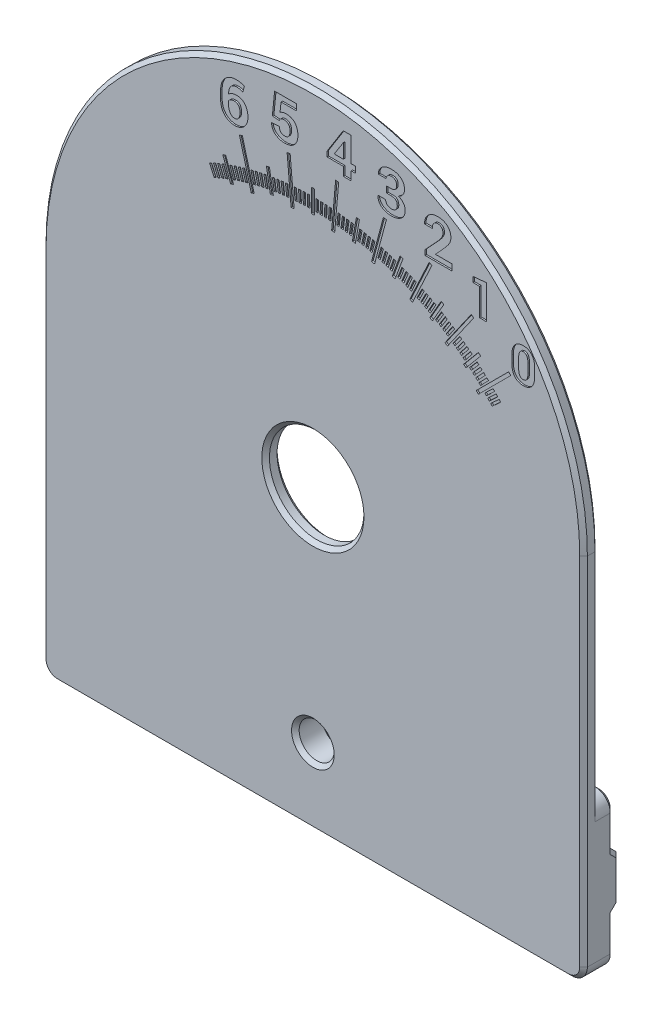
SolidWorks part; units mm, degrees
ref_plane "Front" through (0, 0, 0) normal (0, 0, 1) x (1, 0, 0)
ref_plane "Top" through (0, 0, 0) normal (0, 1, 0) x (1, 0, 0)
ref_plane "Right" through (0, 0, 0) normal (1, 0, 0) x (0, 0, -1)
sketch "Skizze1" plane through (0, 0, 0) normal (0, 0, 1) x (1, 0, 0)
  line L0 (0, 0) -> (35.5, 0)
  line L1 (0, 0) -> (0, 30.7358) construction
  line L2 (35.5, 5.5) -> (35.5, 0) construction
  line L3 (35.5, 0) -> (35.5, 28.6879)
  line L4 (-35.5, 0) -> (-35.5, 28.6879)
  line L5 (35.5, 0) -> (35.5, -20)
  line L6 (35.5, -20) -> (-35.5, -20)
  line L7 (-35.5, -20) -> (-35.5, 0)
  line L8 (-35.5, 0) -> (0, 0)
  arc A1 (35.5, 28.6879) -> (0, 64.1879) centre (0, 28.6879) ccw
  arc A2 (-35.5, 28.6879) -> (0, 64.1879) centre (0, 28.6879) cw
  dimension "D1" = 20
extrude "Aufsatz-Linear austragen1" add sketch "Skizze1" along normal blind 2 contours A2 L4 L8 L0 L3 A1 region at (0, 28.8397, 0)
sketch "Skizze2" plane through (0, 0, 2) normal (0, 0, 1) x (1, 0, 0)
  line L0 (0, 19) -> (0, 51.4601) construction
  line L1 (0, 19) -> (13.7352, 32.7352) construction
  line L2 (0, 19) -> (3.1812, 55.3611) construction
  line L3 (2.8575, 49.3665) -> (3.3804, 55.3437)
  line L4 (2.8575, 49.3665) -> (2.459, 49.4014)
  line L5 (3.3804, 55.3437) -> (3.1812, 55.3611)
  line L6 (2.9819, 55.3785) -> (3.1812, 55.3611)
  line L7 (2.459, 49.4014) -> (2.9819, 55.3785)
  line L8 (0, 19) -> (-2.3131, -14.0789) construction
  line L9 (2.3019, 51.9193) -> (2.4516, 51.9088)
  line L10 (2.4516, 51.9088) -> (2.3469, 50.4124)
  line L11 (2.3469, 50.4124) -> (2.0477, 50.4334)
  line L12 (2.1523, 51.9297) -> (2.0477, 50.4334)
  line L13 (2.3019, 51.9193) -> (2.1523, 51.9297)
  line L14 (0, 19) -> (-1.6664, -8.2459) construction
  line L15 (0, 19) -> (-1.7354, -14.1142) construction
  line L16 (1.5773, 51.9623) -> (1.4988, 50.4643)
  line L17 (1.7271, 51.9544) -> (1.5773, 51.9623)
  line L18 (1.7271, 51.9544) -> (1.8769, 51.9466)
  line L19 (1.8769, 51.9466) -> (1.7984, 50.4486)
  line L20 (1.4988, 50.4643) -> (1.7984, 50.4486)
  line L21 (0, 19) -> (-1.1573, -14.1395) construction
  line L22 (1.0018, 51.9848) -> (0.9494, 50.4857)
  line L23 (1.1517, 51.9795) -> (1.0018, 51.9848)
  line L24 (1.1517, 51.9795) -> (1.3016, 51.9743)
  line L25 (1.3016, 51.9743) -> (1.2492, 50.4752)
  line L26 (0.9494, 50.4857) -> (1.2492, 50.4752)
  line L27 (0, 19) -> (0, -14.1597) construction
  line L28 (0, 19) -> (-0.5787, -14.1546) construction
  line L34 (0.5759, 51.9946) -> (0.7259, 51.992)
  line L35 (0.5759, 51.9946) -> (0.4259, 51.9972)
  line L36 (0.4259, 51.9972) -> (0.3998, 50.4975)
  line L37 (0.6997, 50.4922) -> (0.3998, 50.4975)
  line L38 (0.7259, 51.992) -> (0.6997, 50.4922)
  line L39 (0, 53) -> (0.2, 53)
  line L40 (0.2, 53) -> (0.2, 50)
  line L41 (0.2, 50) -> (-0.2, 50)
  line L42 (-0.2, 53) -> (-0.2, 50)
  line L43 (0, 53) -> (-0.2, 53)
  line L44 (-2.4516, 51.9088) -> (-2.3469, 50.4124)
  line L45 (-2.3019, 51.9193) -> (-2.4516, 51.9088)
  line L46 (-2.3019, 51.9193) -> (-2.1523, 51.9297)
  line L47 (-2.1523, 51.9297) -> (-2.0477, 50.4334)
  line L48 (-2.3469, 50.4124) -> (-2.0477, 50.4334)
  line L49 (-1.7271, 51.9544) -> (-1.5773, 51.9623)
  line L50 (-1.7271, 51.9544) -> (-1.8769, 51.9466)
  line L51 (-1.8769, 51.9466) -> (-1.7984, 50.4486)
  line L52 (-1.4988, 50.4643) -> (-1.7984, 50.4486)
  line L53 (-1.5773, 51.9623) -> (-1.4988, 50.4643)
  line L54 (-1.1517, 51.9795) -> (-1.0018, 51.9848)
  line L55 (-1.1517, 51.9795) -> (-1.3016, 51.9743)
  line L56 (-1.3016, 51.9743) -> (-1.2492, 50.4752)
  line L57 (-0.9494, 50.4857) -> (-1.2492, 50.4752)
  line L58 (-1.0018, 51.9848) -> (-0.9494, 50.4857)
  line L59 (-0.5759, 51.9946) -> (-0.4259, 51.9972)
  line L60 (-0.4259, 51.9972) -> (-0.3998, 50.4975)
  line L61 (-0.6997, 50.4922) -> (-0.3998, 50.4975)
  line L62 (-0.7259, 51.992) -> (-0.6997, 50.4922)
  line L63 (-0.5759, 51.9946) -> (-0.7259, 51.992)
  line L64 (-2.459, 49.4014) -> (-2.9819, 55.3785)
  line L65 (-2.8575, 49.3665) -> (-2.459, 49.4014)
  line L66 (-2.8575, 49.3665) -> (-3.3804, 55.3437)
  line L67 (-3.3804, 55.3437) -> (-3.1812, 55.3611)
  line L68 (-2.9819, 55.3785) -> (-3.1812, 55.3611)
  line L69 (0, 19) -> (-3.1812, 55.3611) construction
  line L70 (-5.1623, 51.5934) -> (-5.0141, 51.6168)
  line L71 (-5.0141, 51.6168) -> (-4.7795, 50.1353)
  line L72 (-4.7795, 50.1353) -> (-5.0758, 50.0884)
  line L73 (-5.3104, 51.5699) -> (-5.0758, 50.0884)
  line L74 (-5.1623, 51.5934) -> (-5.3104, 51.5699)
  line L75 (-4.5927, 51.6785) -> (-4.4441, 51.6994)
  line L76 (-4.4441, 51.6994) -> (-4.2354, 50.214)
  line L77 (-4.5324, 50.1722) -> (-4.2354, 50.214)
  line L78 (-4.7412, 51.6576) -> (-4.5324, 50.1722)
  line L79 (-4.5927, 51.6785) -> (-4.7412, 51.6576)
  line L80 (-4.0216, 51.7537) -> (-3.8728, 51.7719)
  line L81 (-3.8728, 51.7719) -> (-3.69, 50.2831)
  line L82 (-3.9877, 50.2466) -> (-3.69, 50.2831)
  line L83 (-4.1705, 51.7354) -> (-3.9877, 50.2466)
  line L84 (-4.0216, 51.7537) -> (-4.1705, 51.7354)
  line L85 (-3.4494, 51.8189) -> (-3.3002, 51.8345)
  line L86 (-3.4494, 51.8189) -> (-3.5986, 51.8032)
  line L87 (-3.5986, 51.8032) -> (-3.4418, 50.3114)
  line L88 (-3.1434, 50.3428) -> (-3.4418, 50.3114)
  line L89 (-3.3002, 51.8345) -> (-3.1434, 50.3428)
  line L90 (-6.101, 52.4487) -> (-5.5801, 49.4943)
  line L91 (-5.904, 52.4835) -> (-6.101, 52.4487)
  line L92 (-5.904, 52.4835) -> (-5.7071, 52.5182)
  line L93 (-5.7071, 52.5182) -> (-5.1861, 49.5638)
  line L94 (-5.5801, 49.4943) -> (-5.1861, 49.5638)
  line L95 (0, 19) -> (-5.6366, 50.967) construction
  line L96 (0, 19) -> (-9.4469, 54.2563) construction
  line L97 (-7.7008, 48.5125) -> (-8.0872, 48.409)
  line L98 (-7.7008, 48.5125) -> (-9.2537, 54.3081)
  line L99 (-9.2537, 54.3081) -> (-9.4469, 54.2563)
  line L100 (-9.6401, 54.2045) -> (-9.4469, 54.2563)
  line L101 (-8.0872, 48.409) -> (-9.6401, 54.2045)
  line L102 (-7.9833, 51.0194) -> (-7.8378, 51.0557)
  line L103 (-7.8378, 51.0557) -> (-7.4749, 49.6003)
  line L104 (-7.766, 49.5277) -> (-7.4749, 49.6003)
  line L105 (-8.1289, 50.9831) -> (-7.766, 49.5277)
  line L106 (-7.9833, 51.0194) -> (-8.1289, 50.9831)
  line L107 (-7.4233, 51.1539) -> (-7.2771, 51.1876)
  line L108 (-7.2771, 51.1876) -> (-6.9397, 49.7261)
  line L109 (-6.9397, 49.7261) -> (-7.232, 49.6586)
  line L110 (-7.5695, 51.1201) -> (-7.232, 49.6586)
  line L111 (-7.4233, 51.1539) -> (-7.5695, 51.1201)
  line L112 (-6.861, 51.2785) -> (-6.7143, 51.3097)
  line L113 (-6.7143, 51.3097) -> (-6.4024, 49.8425)
  line L114 (-6.4024, 49.8425) -> (-6.6959, 49.7801)
  line L115 (-7.0077, 51.2473) -> (-6.6959, 49.7801)
  line L116 (-6.861, 51.2785) -> (-7.0077, 51.2473)
  line L117 (-6.2966, 51.3933) -> (-6.1494, 51.422)
  line L118 (-6.1494, 51.422) -> (-5.8632, 49.9495)
  line L119 (-6.1577, 49.8923) -> (-5.8632, 49.9495)
  line L120 (-6.4439, 51.3647) -> (-6.1577, 49.8923)
  line L121 (-6.2966, 51.3933) -> (-6.4439, 51.3647)
  line L122 (0, 19) -> (-11.102, 49.5026) construction
  line L123 (-11.6287, 50.9495) -> (-11.4407, 51.018)
  line L124 (-11.6287, 50.9495) -> (-11.8166, 50.8811)
  line L125 (-11.8166, 50.8811) -> (-10.7906, 48.0621)
  line L126 (-10.4147, 48.1989) -> (-10.7906, 48.0621)
  line L127 (-11.4407, 51.018) -> (-10.4147, 48.1989)
  line L128 (-10.7436, 50.2018) -> (-10.6018, 50.2506)
  line L129 (-10.6018, 50.2506) -> (-10.1135, 48.8323)
  line L130 (-10.1135, 48.8323) -> (-10.3971, 48.7347)
  line L131 (-10.8855, 50.1529) -> (-10.3971, 48.7347)
  line L132 (-10.7436, 50.2018) -> (-10.8855, 50.1529)
  line L133 (-10.1975, 50.3845) -> (-10.0548, 50.4309)
  line L134 (-10.0548, 50.4309) -> (-9.5913, 49.0043)
  line L135 (-9.8766, 48.9116) -> (-9.5913, 49.0043)
  line L136 (-10.3401, 50.3382) -> (-9.8766, 48.9116)
  line L137 (-10.1975, 50.3845) -> (-10.3401, 50.3382)
  line L138 (-9.6482, 50.5577) -> (-9.5047, 50.6016)
  line L139 (-9.5047, 50.6016) -> (-9.0662, 49.1671)
  line L140 (-9.353, 49.0794) -> (-9.0662, 49.1671)
  line L141 (-9.7916, 50.5139) -> (-9.353, 49.0794)
  line L142 (-9.6482, 50.5577) -> (-9.7916, 50.5139)
  line L143 (-9.0959, 50.7213) -> (-8.9517, 50.7626)
  line L144 (-8.9517, 50.7626) -> (-8.5383, 49.3207)
  line L145 (-8.5383, 49.3207) -> (-8.8267, 49.2381)
  line L146 (-9.2401, 50.6799) -> (-8.8267, 49.2381)
  line L147 (-9.0959, 50.7213) -> (-9.2401, 50.6799)
  line L148 (-13.4222, 49.1467) -> (-13.2851, 49.2077)
  line L149 (-13.2851, 49.2077) -> (-12.675, 47.8374)
  line L150 (-12.9491, 47.7153) -> (-12.675, 47.8374)
  line L151 (-13.5592, 49.0857) -> (-12.9491, 47.7153)
  line L152 (-13.4222, 49.1467) -> (-13.5592, 49.0857)
  line L153 (-12.894, 49.3763) -> (-12.7559, 49.4349)
  line L154 (-12.7559, 49.4349) -> (-12.1698, 48.0542)
  line L155 (-12.1698, 48.0542) -> (-12.446, 47.937)
  line L156 (-13.0321, 49.3177) -> (-12.446, 47.937)
  line L157 (-12.894, 49.3763) -> (-13.0321, 49.3177)
  line L158 (-12.3619, 49.5967) -> (-12.2228, 49.6529)
  line L159 (-12.2228, 49.6529) -> (-11.6609, 48.2622)
  line L160 (-11.6609, 48.2622) -> (-11.9391, 48.1498)
  line L161 (-12.501, 49.5405) -> (-11.9391, 48.1498)
  line L162 (-12.3619, 49.5967) -> (-12.501, 49.5405)
  line L163 (-11.826, 49.8078) -> (-11.686, 49.8616)
  line L164 (-11.686, 49.8616) -> (-11.1484, 48.4612)
  line L165 (-11.4285, 48.3537) -> (-11.1484, 48.4612)
  line L166 (-11.9661, 49.7541) -> (-11.4285, 48.3537)
  line L167 (-11.826, 49.8078) -> (-11.9661, 49.7541)
  line L168 (3.3002, 51.8345) -> (3.1434, 50.3428)
  line L169 (3.4494, 51.8189) -> (3.3002, 51.8345)
  line L170 (3.4494, 51.8189) -> (3.5986, 51.8032)
  line L171 (3.5986, 51.8032) -> (3.4418, 50.3114)
  line L172 (3.1434, 50.3428) -> (3.4418, 50.3114)
  line L173 (4.0216, 51.7537) -> (4.1705, 51.7354)
  line L174 (4.0216, 51.7537) -> (3.8728, 51.7719)
  line L175 (3.8728, 51.7719) -> (3.69, 50.2831)
  line L176 (3.9877, 50.2466) -> (3.69, 50.2831)
  line L177 (4.1705, 51.7354) -> (3.9877, 50.2466)
  line L178 (4.5927, 51.6785) -> (4.7412, 51.6576)
  line L179 (4.5927, 51.6785) -> (4.4441, 51.6994)
  line L180 (4.4441, 51.6994) -> (4.2354, 50.214)
  line L181 (4.5324, 50.1722) -> (4.2354, 50.214)
  line L182 (4.7412, 51.6576) -> (4.5324, 50.1722)
  line L183 (5.1623, 51.5934) -> (5.3104, 51.5699)
  line L184 (5.3104, 51.5699) -> (5.0758, 50.0884)
  line L185 (4.7795, 50.1353) -> (5.0758, 50.0884)
  line L186 (5.0141, 51.6168) -> (4.7795, 50.1353)
  line L187 (5.1623, 51.5934) -> (5.0141, 51.6168)
  line L188 (0, 19) -> (5.6366, 50.967) construction
  line L189 (5.7071, 52.5182) -> (5.1861, 49.5638)
  line L190 (5.904, 52.4835) -> (5.7071, 52.5182)
  line L191 (5.904, 52.4835) -> (6.101, 52.4487)
  line L192 (6.101, 52.4487) -> (5.5801, 49.4943)
  line L193 (5.1861, 49.5638) -> (5.5801, 49.4943)
  line L194 (6.2966, 51.3933) -> (6.4439, 51.3647)
  line L195 (6.4439, 51.3647) -> (6.1577, 49.8923)
  line L196 (6.1577, 49.8923) -> (5.8632, 49.9495)
  line L197 (6.1494, 51.422) -> (5.8632, 49.9495)
  line L198 (6.2966, 51.3933) -> (6.1494, 51.422)
  line L199 (6.861, 51.2785) -> (7.0077, 51.2473)
  line L200 (7.0077, 51.2473) -> (6.6959, 49.7801)
  line L201 (6.4024, 49.8425) -> (6.6959, 49.7801)
  line L202 (6.7143, 51.3097) -> (6.4024, 49.8425)
  line L203 (6.861, 51.2785) -> (6.7143, 51.3097)
  line L204 (7.4233, 51.1539) -> (7.5695, 51.1201)
  line L205 (7.5695, 51.1201) -> (7.232, 49.6586)
  line L206 (6.9397, 49.7261) -> (7.232, 49.6586)
  line L207 (7.2771, 51.1876) -> (6.9397, 49.7261)
  line L208 (7.4233, 51.1539) -> (7.2771, 51.1876)
  line L209 (7.9833, 51.0194) -> (8.1289, 50.9831)
  line L210 (7.9833, 51.0194) -> (7.8378, 51.0557)
  line L211 (7.8378, 51.0557) -> (7.4749, 49.6003)
  line L212 (7.766, 49.5277) -> (7.4749, 49.6003)
  line L213 (8.1289, 50.9831) -> (7.766, 49.5277)
  line L214 (0, 19) -> (9.4469, 54.2563) construction
  line L215 (8.0872, 48.409) -> (9.6401, 54.2045)
  line L216 (7.7008, 48.5125) -> (8.0872, 48.409)
  line L217 (7.7008, 48.5125) -> (9.2537, 54.3081)
  line L218 (9.2537, 54.3081) -> (9.4469, 54.2563)
  line L219 (9.6401, 54.2045) -> (9.4469, 54.2563)
  line L220 (9.0959, 50.7213) -> (9.2401, 50.6799)
  line L221 (9.2401, 50.6799) -> (8.8267, 49.2381)
  line L222 (8.5383, 49.3207) -> (8.8267, 49.2381)
  line L223 (8.9517, 50.7626) -> (8.5383, 49.3207)
  line L224 (9.0959, 50.7213) -> (8.9517, 50.7626)
  line L225 (9.6482, 50.5577) -> (9.7916, 50.5139)
  line L226 (9.7916, 50.5139) -> (9.353, 49.0794)
  line L227 (9.353, 49.0794) -> (9.0662, 49.1671)
  line L228 (9.5047, 50.6016) -> (9.0662, 49.1671)
  line L229 (9.6482, 50.5577) -> (9.5047, 50.6016)
  line L230 (10.1975, 50.3845) -> (10.3401, 50.3382)
  line L231 (10.3401, 50.3382) -> (9.8766, 48.9116)
  line L232 (9.8766, 48.9116) -> (9.5913, 49.0043)
  line L233 (10.0548, 50.4309) -> (9.5913, 49.0043)
  line L234 (10.1975, 50.3845) -> (10.0548, 50.4309)
  line L235 (10.7436, 50.2018) -> (10.8855, 50.1529)
  line L236 (10.8855, 50.1529) -> (10.3971, 48.7347)
  line L237 (10.1135, 48.8323) -> (10.3971, 48.7347)
  line L238 (10.6018, 50.2506) -> (10.1135, 48.8323)
  line L239 (10.7436, 50.2018) -> (10.6018, 50.2506)
  line L240 (0, 19) -> (11.102, 49.5026) construction
  line L241 (11.6287, 50.9495) -> (11.8166, 50.8811)
  line L242 (11.6287, 50.9495) -> (11.4407, 51.018)
  line L243 (11.4407, 51.018) -> (10.4147, 48.1989)
  line L244 (10.7906, 48.0621) -> (10.4147, 48.1989)
  line L245 (11.8166, 50.8811) -> (10.7906, 48.0621)
  line L246 (11.826, 49.8078) -> (11.9661, 49.7541)
  line L247 (11.9661, 49.7541) -> (11.4285, 48.3537)
  line L248 (11.4285, 48.3537) -> (11.1484, 48.4612)
  line L249 (11.686, 49.8616) -> (11.1484, 48.4612)
  line L250 (11.826, 49.8078) -> (11.686, 49.8616)
  line L251 (12.3619, 49.5967) -> (12.501, 49.5405)
  line L252 (12.501, 49.5405) -> (11.9391, 48.1498)
  line L253 (11.6609, 48.2622) -> (11.9391, 48.1498)
  line L254 (12.2228, 49.6529) -> (11.6609, 48.2622)
  line L255 (12.3619, 49.5967) -> (12.2228, 49.6529)
  line L256 (12.894, 49.3763) -> (13.0321, 49.3177)
  line L257 (13.0321, 49.3177) -> (12.446, 47.937)
  line L258 (12.1698, 48.0542) -> (12.446, 47.937)
  line L259 (12.7559, 49.4349) -> (12.1698, 48.0542)
  line L260 (12.894, 49.3763) -> (12.7559, 49.4349)
  line L261 (13.4222, 49.1467) -> (13.5592, 49.0857)
  line L262 (13.5592, 49.0857) -> (12.9491, 47.7153)
  line L263 (12.9491, 47.7153) -> (12.675, 47.8374)
  line L264 (13.2851, 49.2077) -> (12.675, 47.8374)
  line L265 (13.4222, 49.1467) -> (13.2851, 49.2077)
  line L266 (0, 19) -> (15.4256, 52.0802) construction
  line L267 (13.0711, 46.5579) -> (12.7086, 46.7269)
  line L268 (13.0711, 46.5579) -> (15.6068, 51.9957)
  line L269 (15.6068, 51.9957) -> (15.4256, 52.0802)
  line L270 (15.2443, 52.1648) -> (15.4256, 52.0802)
  line L271 (12.7086, 46.7269) -> (15.2443, 52.1648)
  line L272 (21.8548, 45.0455) -> (22.008, 44.917)
  line L273 (21.8548, 45.0455) -> (21.7016, 45.1741)
  line L274 (21.7016, 45.1741) -> (19.7732, 42.8759)
  line L275 (20.0796, 42.6188) -> (19.7732, 42.8759)
  line L276 (22.008, 44.917) -> (20.0796, 42.6188)
  line L277 (20.7673, 44.6455) -> (20.8839, 44.5511)
  line L278 (20.8839, 44.5511) -> (19.9399, 43.3854)
  line L279 (19.7068, 43.5742) -> (19.9399, 43.3854)
  line L280 (20.6508, 44.7399) -> (19.7068, 43.5742)
  line L281 (20.7673, 44.6455) -> (20.6508, 44.7399)
  line L282 (20.3166, 45.0041) -> (20.4348, 44.9117)
  line L283 (20.4348, 44.9117) -> (19.5113, 43.7297)
  line L284 (19.5113, 43.7297) -> (19.2749, 43.9144)
  line L285 (20.1984, 45.0964) -> (19.2749, 43.9144)
  line L286 (20.3166, 45.0041) -> (20.1984, 45.0964)
  line L287 (19.8597, 45.3547) -> (19.9795, 45.2644)
  line L288 (19.9795, 45.2644) -> (19.0768, 44.0665)
  line L289 (19.0768, 44.0665) -> (18.8372, 44.247)
  line L290 (19.7399, 45.445) -> (18.8372, 44.247)
  line L291 (19.8597, 45.3547) -> (19.7399, 45.445)
  line L292 (19.3967, 45.6973) -> (19.5181, 45.6091)
  line L293 (19.5181, 45.6091) -> (18.6364, 44.3956)
  line L294 (18.3937, 44.5719) -> (18.6364, 44.3956)
  line L295 (19.2754, 45.7854) -> (18.3937, 44.5719)
  line L296 (19.3967, 45.6973) -> (19.2754, 45.7854)
  line L297 (17.6579, 43.8694) -> (17.3303, 44.0989)
  line L298 (17.6579, 43.8694) -> (21.0994, 48.7843)
  line L299 (21.0994, 48.7843) -> (20.9355, 48.899)
  line L300 (20.7717, 49.0138) -> (20.9355, 48.899)
  line L301 (17.3303, 44.0989) -> (20.7717, 49.0138)
  line L302 (18.4532, 46.3579) -> (18.5775, 46.2741)
  line L303 (18.5775, 46.2741) -> (17.7387, 45.0305)
  line L304 (17.7387, 45.0305) -> (17.49, 45.1983)
  line L305 (18.3288, 46.4418) -> (17.49, 45.1983)
  line L306 (18.4532, 46.3579) -> (18.3288, 46.4418)
  line L307 (17.9729, 46.6758) -> (18.0987, 46.5941)
  line L308 (18.0987, 46.5941) -> (17.2817, 45.3361)
  line L309 (17.0301, 45.4995) -> (17.2817, 45.3361)
  line L310 (17.8471, 46.7575) -> (17.0301, 45.4995)
  line L311 (17.9729, 46.6758) -> (17.8471, 46.7575)
  line L312 (17.4871, 46.9853) -> (17.6144, 46.9058)
  line L313 (17.6144, 46.9058) -> (16.8195, 45.6337)
  line L314 (16.5651, 45.7927) -> (16.8195, 45.6337)
  line L315 (17.3599, 47.0648) -> (16.5651, 45.7927)
  line L316 (17.4871, 46.9853) -> (17.3599, 47.0648)
  line L317 (16.9961, 47.2862) -> (17.1246, 47.209)
  line L318 (17.1246, 47.209) -> (16.3521, 45.9232)
  line L319 (16.3521, 45.9232) -> (16.0949, 46.0777)
  line L320 (16.8675, 47.3635) -> (16.0949, 46.0777)
  line L321 (16.9961, 47.2862) -> (16.8675, 47.3635)
  line L322 (17, 48.4449) -> (17.1732, 48.3449)
  line L323 (17.1732, 48.3449) -> (15.6732, 45.7468)
  line L324 (15.3268, 45.9468) -> (15.6732, 45.7468)
  line L325 (16.8268, 48.5449) -> (15.3268, 45.9468)
  line L326 (17, 48.4449) -> (16.8268, 48.5449)
  line L327 (15.9985, 47.8621) -> (16.1297, 47.7894)
  line L328 (16.1297, 47.7894) -> (15.4025, 46.4775)
  line L329 (15.1401, 46.6229) -> (15.4025, 46.4775)
  line L330 (15.8674, 47.9349) -> (15.1401, 46.6229)
  line L331 (15.9985, 47.8621) -> (15.8674, 47.9349)
  line L332 (15.4924, 48.137) -> (15.6248, 48.0665)
  line L333 (15.6248, 48.0665) -> (14.9206, 46.7421)
  line L334 (14.9206, 46.7421) -> (14.6557, 46.883)
  line L335 (15.36, 48.2074) -> (14.6557, 46.883)
  line L336 (15.4924, 48.137) -> (15.36, 48.2074)
  line L337 (14.9815, 48.4029) -> (15.1152, 48.3348)
  line L338 (15.1152, 48.3348) -> (14.4342, 46.9983)
  line L339 (14.4342, 46.9983) -> (14.1669, 47.1345)
  line L340 (14.8479, 48.471) -> (14.1669, 47.1345)
  line L341 (14.9815, 48.4029) -> (14.8479, 48.471)
  line L342 (14.4661, 48.6599) -> (14.6009, 48.5941)
  line L343 (14.6009, 48.5941) -> (13.9434, 47.2459)
  line L344 (13.6737, 47.3774) -> (13.9434, 47.2459)
  line L345 (14.3313, 48.7256) -> (13.6737, 47.3774)
  line L346 (14.4661, 48.6599) -> (14.3313, 48.7256)
  line L347 (0, 19) -> (20.865, 43.8659) construction
  line L348 (24.5235, 41.0811) -> (24.6239, 40.9696)
  line L349 (24.6239, 40.9696) -> (23.5092, 39.9659)
  line L350 (23.5092, 39.9659) -> (23.3084, 40.1888)
  line L351 (24.4231, 41.1925) -> (23.3084, 40.1888)
  line L352 (24.5235, 41.0811) -> (24.4231, 41.1925)
  line L353 (24.1344, 41.5057) -> (24.2367, 41.396)
  line L354 (24.2367, 41.396) -> (23.1397, 40.373)
  line L355 (23.1397, 40.373) -> (22.9351, 40.5924)
  line L356 (24.0321, 41.6154) -> (22.9351, 40.5924)
  line L357 (24.1344, 41.5057) -> (24.0321, 41.6154)
  line L358 (23.738, 41.9235) -> (23.8422, 41.8156)
  line L359 (23.8422, 41.8156) -> (22.7631, 40.7736)
  line L360 (22.5547, 40.9894) -> (22.7631, 40.7736)
  line L361 (23.6338, 42.0314) -> (22.5547, 40.9894)
  line L362 (23.738, 41.9235) -> (23.6338, 42.0314)
  line L363 (21.4253, 40.7082) -> (25.668, 44.9508)
  line L364 (25.668, 44.9508) -> (25.8094, 44.8094)
  line L365 (25.9508, 44.668) -> (25.8094, 44.8094)
  line L366 (21.7082, 40.4253) -> (25.9508, 44.668)
  line L367 (21.4253, 40.7082) -> (21.7082, 40.4253)
  line L368 (22.9235, 42.738) -> (23.0314, 42.6338)
  line L369 (23.0314, 42.6338) -> (21.9894, 41.5547)
  line L370 (21.9894, 41.5547) -> (21.7736, 41.7631)
  line L371 (22.8156, 42.8422) -> (21.7736, 41.7631)
  line L372 (22.9235, 42.738) -> (22.8156, 42.8422)
  line L373 (22.5057, 43.1344) -> (22.6154, 43.0321)
  line L374 (22.6154, 43.0321) -> (21.5924, 41.9351)
  line L375 (21.373, 42.1397) -> (21.5924, 41.9351)
  line L376 (22.396, 43.2367) -> (21.373, 42.1397)
  line L377 (22.5057, 43.1344) -> (22.396, 43.2367)
  line L378 (22.0811, 43.5235) -> (22.1925, 43.4231)
  line L379 (22.1925, 43.4231) -> (21.1888, 42.3084)
  line L380 (20.9659, 42.5092) -> (21.1888, 42.3084)
  line L381 (21.9696, 43.6239) -> (20.9659, 42.5092)
  line L382 (22.0811, 43.5235) -> (21.9696, 43.6239)
  line L383 (21.6497, 43.9051) -> (21.7629, 43.8067)
  line L384 (21.7629, 43.8067) -> (20.7788, 42.6747)
  line L385 (20.7788, 42.6747) -> (20.5524, 42.8715)
  line L386 (21.5365, 44.0036) -> (20.5524, 42.8715)
  line L387 (21.6497, 43.9051) -> (21.5365, 44.0036)
  circle A1 centre (0, 19) radius 31.5 construction
  point P7 (0, 50.5)
  point P14 (2.6583, 49.3839)
  point P22 (2.1973, 50.4229)
  point P39 (0, 50)
  point P392 (2.7454, 50.3801)
  dimension "D11" = 63
  dimension "D1" = 45
  dimension "D2" = 5
  dimension "D3" = 0.4
  dimension "D4" = 6
  dimension "D5" = 1
  dimension "D6" = 1.5
  dimension "D7" = 0.3
  dimension "D8" = 0.5
  dimension "D9" = 0.4
  dimension "D10" = 3
  dimension "D12" = 1
  dimension "D13" = 0.5
extrude "Schnitt-Linear austragen1" cut sketch "Skizze2" against normal blind 0.2
sketch "Skizze4" plane through (0, 0, 2) normal (0, 0, 1) x (1, 0, 0)
  circle A0 centre (0, 19) radius 6.2
  dimension "D1" = 12.4
extrude "Schnitt-Linear austragen2" cut sketch "Skizze4" against normal through all
sketch "Skizze3" plane through (0, 0, 2) normal (0, 0, 1) x (1, 0, 0)
  line L0 (0, 0) -> (0, 74.8793) construction
  line L3 (30.5937, 44.3937) -> (24.5937, 44.3937) construction
  line L4 (19.2468, 49.1883) -> (25.2468, 49.1883) construction
  line L5 (13.4601, 52.6944) -> (19.4601, 52.6944) construction
  line L6 (7.3695, 55.0378) -> (13.3695, 55.0378) construction
  line L7 (0.7176, 56.3153) -> (6.7176, 56.3153) construction
  line L8 (-7.3695, 55.0378) -> (-13.3695, 55.0378) construction
  line L9 (-0.7176, 56.3153) -> (-6.7176, 56.3153) construction
  circle A0 centre (0, 19) radius 37.5 construction
  text T0 "0" font "Roboto" height in points 12
  text T1 "1" font "Roboto" height in points 12
  text T2 "2" font "Roboto" height in points 14
  text T3 "3" font "Roboto" height in points 14
  text T4 "4" font "Roboto" height in points 14
  text T5 "5" font "Roboto" height in points 14
  text T6 "6" font "Roboto" height in points 14
  point P7 (35.8991, 29.8398)
  point P8 (27.5937, 44.3937)
  point P16 (22.2468, 49.1883)
  point P17 (16.4601, 52.6944)
  point P20 (10.3695, 55.0378)
  point P23 (3.7176, 56.3153)
  dimension "D1" = 75
  dimension "D2" = 6
extrude "Schnitt-Linear austragen3" cut sketch "Skizze3" against normal blind 0.2
extrude "Aufsatz-Linear austragen2" add sketch "Skizze1<3>" along normal blind 2 and the other way blind 2 contours L8 L7 L6 L5 L0 region at (0, -10, 0)
sketch "Skizze1<3>" plane through (0, 0, 0) normal (0, 0, 1) x (1, 0, 0) same geometry as "Skizze1"
sketch "Skizze5" plane through (-35.5, 0, 0) normal (-1, 0, 0) x (0, 0, 1)
  line L0 (-2, -10) -> (-12.7757, -10) construction
  line L1 (-2, -20) -> (-2, 0) construction
  line L2 (-2, -13.5) -> (-2, -6.5)
  line L3 (-2, -6.5) -> (-2.75, -7.25)
  line L4 (-2.75, -7.25) -> (-2.75, -12.75)
  line L5 (-2, -13.5) -> (-2.75, -12.75)
  point P9 (-2.75, -10)
  dimension "D1" = 0.75
  dimension "D2" = 7
  dimension "D3" = 45
extrude "Aufsatz-Linear austragen3" add sketch "Skizze5" against normal up to surface (71 mm away) up to face at (35.5, 2.896, 0)
sketch "Skizze6" plane through (0, 0, 2) normal (0, 0, 1) x (1, 0, 0)
  line L0 (0, 0) -> (0, -20) construction
  line L1 (35.5, -20) -> (-35.5, -20) construction
  circle A0 centre (0, -10) radius 2.3
  dimension "D1" = 4.6
extrude "Schnitt-Linear austragen4" cut sketch "Skizze6" against normal through all
sketch "Skizze7" plane through (0, 0, -2) normal (0, 0, -1) x (-1, 0, 0)
  circle A0 centre (0, -10) radius 4.15
  dimension "D1" = 8.3
extrude "Schnitt-Linear austragen5" cut sketch "Skizze7" along normal blind 2
fillet "Verrundung1" radius 1 2 edges at (-4.15, -10, -2.75) (4.15, -10, -2.75)
fillet "Verrundung2" radius 2 4 edges at (35.5, -20, 0) (35.5, 0, -1) (-35.5, 0, -1) (-35.5, -20, 0)
chamfer "Fase1" distance 0.5 angle 45 29 edges at (-35.5, 13.344, 0) (35.5, 13.344, 0) (0, 64.1879, 0) (-2.3, -10, -2) (2.3, -10, 2) (6.2, 19, 2) (6.2, 19, 0) (0, 0, -2) (0, -20, -2) (35.5, 5.344, 2) (0, 64.1879, 2) (0, -20, 2) (-35.5, 5.344, 2) (35.5, -13.125, -2.375) (35.5, -10, -2.75) (35.5, -6.875, -2.375) (35.5, -4.25, -2) (34.9142, -0.5858, -2) (-34.9142, -0.5858, -2) (-35.5, -13.125, -2.375) (-35.5, -10, -2.75) (-35.5, -6.875, -2.375) (-35.5, -4.25, -2) (35.5, -15.75, -2) (-35.5, -15.75, -2) (34.9142, -19.4142, -2) (-34.9142, -19.4142, -2) (34.9142, -19.4142, 2) (-34.9142, -19.4142, 2)
